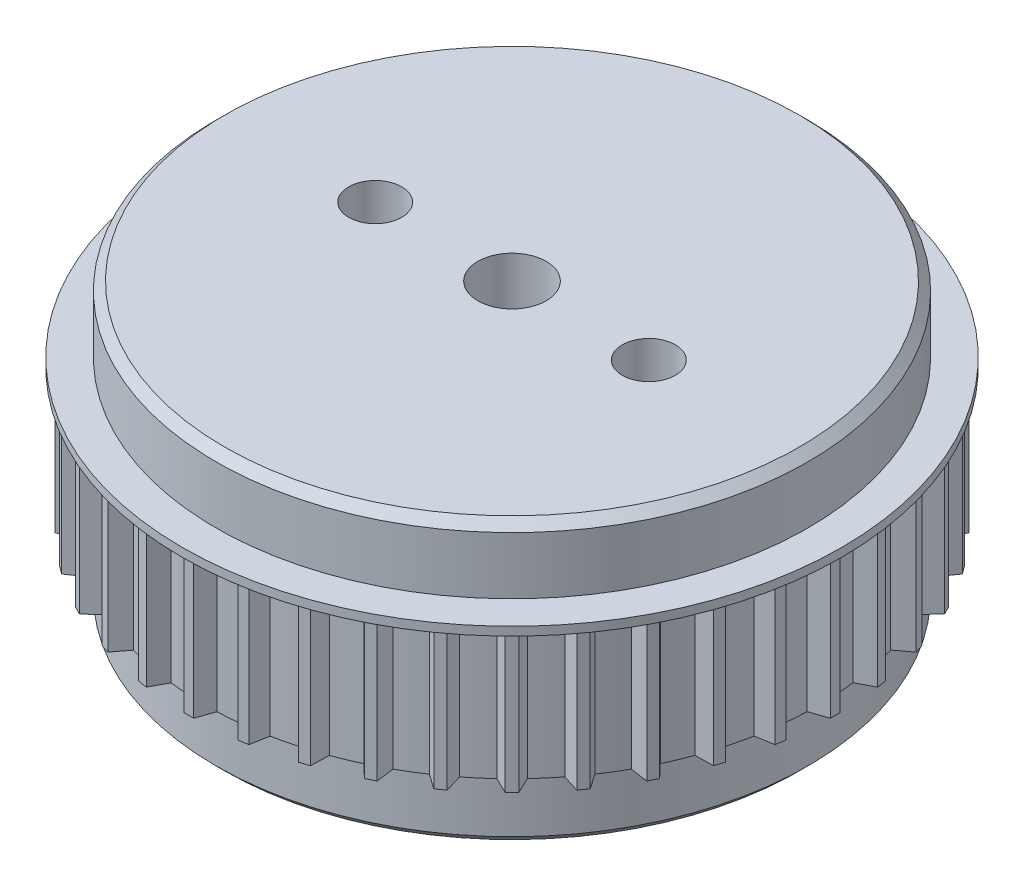
SolidWorks part; units mm, degrees
ref_plane "Front Plane" through (0, 0, 0) normal (0, 0, 1) x (1, 0, 0)
ref_plane "Top Plane" through (0, 0, 0) normal (0, 1, 0) x (1, 0, 0)
ref_plane "Right Plane" through (0, 0, 0) normal (1, 0, 0) x (0, 0, -1)
sketch "Sketch1" plane through (0, 0, 0) normal (0, 1, 0) x (1, 0, 0)
  circle A0 centre (0, 0) radius 17.895
  dimension "D1" = 35.79
extrude "Boss-Extrude1" add sketch "Sketch1" along normal blind 8.2 contours A0
sketch "Sketch2" plane through (0, 8.2, 0) normal (0, 1, 0) x (1, 0, 0)
  line L10 (18.895, 0) -> (18.895, -0.28)
  line L11 (18.895, 0) -> (18.895, 0.28)
  line L12 (18.895, -0.28) -> (17.6307, -0.709)
  line L13 (18.895, 0.28) -> (17.6301, 0.7245)
  arc A4 (17.6307, -0.709) -> (17.6301, 0.7245) centre (0, 0) ccw
  point P6 (18.895, 0)
  dimension "D1" = 6.3369
  dimension "D6" = 1.3351
  dimension "D8" = 17.645
  dimension "D3" = 18.895
  dimension "D4" = 0.28
  dimension "D5" = 0.28
  dimension "D7" = 1.3407
extrude "Boss-Extrude2" add sketch "Sketch2" against normal blind 8.2
pattern_circular "CirPattern1" count 40 over 360 about axis through (0, 8.2, 0) along (0, -1, 0) of "Boss-Extrude1"
pattern_circular "CirPattern2" count 40 over 360 about axis through (0, 8.2, 0) along (0, -1, 0) of "Boss-Extrude1"
pattern_circular "CirPattern4" count 40 over 360 about axis through (0, 8.2, 0) along (0, -1, 0) of "Boss-Extrude2"
sketch "Sketch3" plane through (0, 8.2, 0) normal (0, 1, 0) x (1, 0, 0)
  circle A0 centre (0, 0) radius 19.28
  dimension "D1" = 38.56
extrude "Boss-Extrude3" add sketch "Sketch3" along normal blind 0.5
sketch "Sketch4" plane through (0, 0, 0) normal (0, -1, 0) x (1, 0, 0)
  circle A0 centre (0, 0) radius 17.31
  dimension "D1" = 34.62
extrude "Boss-Extrude4" add sketch "Sketch4" along normal blind 3.85
sketch "Sketch5" plane through (0, 8.7, 0) normal (0, 1, 0) x (1, 0, 0)
  circle A0 centre (0, 0) radius 17.31
  dimension "D1" = 34.62
extrude "Boss-Extrude5" add sketch "Sketch5" along normal blind 3.85
chamfer "Chamfer1" distance 0.5 angle 45 1 edges at (0, -3.85, -17.31)
chamfer "Chamfer2" distance 0.5 angle 45 1 edges at (0, 12.55, 17.31)
sketch "Sketch6" plane through (0, -3.85, 0) normal (0, -1, 0) x (1, 0, 0)
  circle A0 centre (0, 0) radius 2
  dimension "D1" = 4
extrude "Cut-Extrude1" cut sketch "Sketch6" against normal through all
sketch "Sketch7" plane through (0, -3.85, 0) normal (0, -1, 0) x (1, 0, 0)
  circle A1 centre (-8, 0) radius 1.55
  circle A2 centre (8, 0) radius 1.55
  point P0 (-8, 0)
  point P1 (8, 0)
  dimension "D3" = 3.1
  dimension "D4" = 3.1
  dimension "D1" = 8
  dimension "D2" = 8
extrude "Cut-Extrude2" cut sketch "Sketch7" against normal through all
